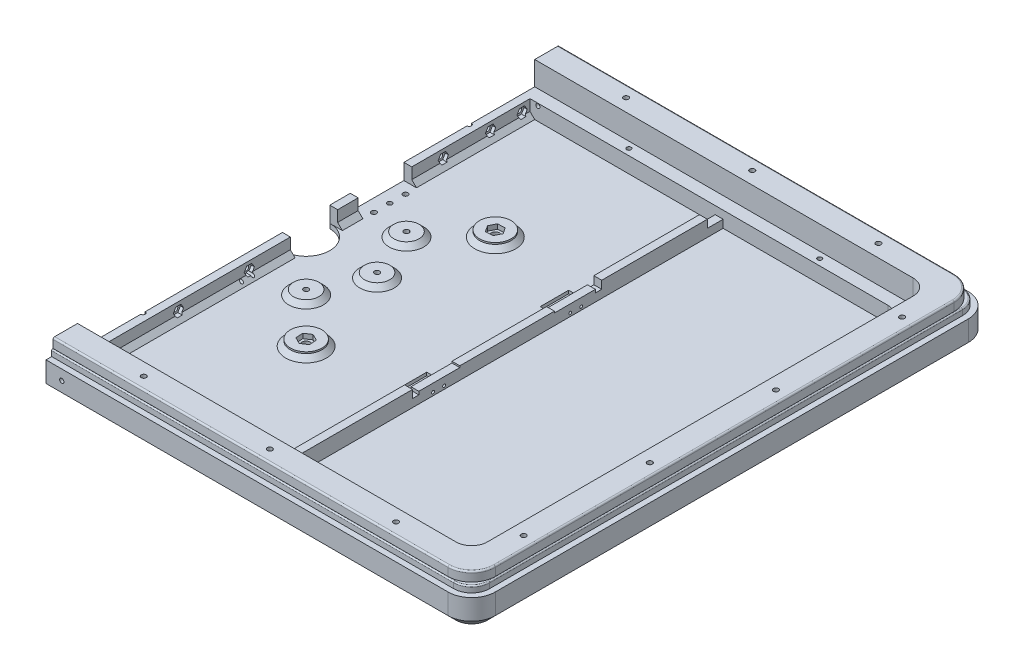
SolidWorks part; units mm, degrees
ref_plane "Front Plane" through (0, 0, 0) normal (0, 0, 1) x (1, 0, 0)
ref_plane "Top Plane" through (0, 0, 0) normal (0, 1, 0) x (1, 0, 0)
ref_plane "Right Plane" through (0, 0, 0) normal (1, 0, 0) x (0, 0, -1)
sketch "Sketch1" plane through (0, 0, 0) normal (0, 1, 0) x (1, 0, 0)
  line L1 (-270, -165) -> (270, -165)
  line L2 (-270, -165) -> (-270, 165)
  line L3 (-270, 165) -> (270, 165)
  line L4 (270, -165) -> (270, 165)
  line L5 (-270, -165) -> (270, 165) construction
  line L6 (-270, 165) -> (270, -165) construction
  point P0 (0, 0)
  dimension "D1" = 540
  dimension "D2" = 330
extrude "Boss-Extrude1" add sketch "Sketch1" along normal blind 3
sketch "Sketch2" plane through (0, 3, 0) normal (0, 1, 0) x (1, 0, 0)
  line L0 (250, 145) -> (-250, 145)
  line L1 (270, -165) -> (-270, -165)
  line L2 (270, -165) -> (270, 165)
  line L3 (270, 165) -> (-270, 165)
  line L4 (-270, -165) -> (-270, 165)
  line L5 (270, -165) -> (-270, 165) construction
  line L6 (270, 165) -> (-270, -165) construction
  line L7 (-250, -145) -> (-250, 145)
  line L8 (250, -145) -> (-250, -145)
  line L9 (250, -145) -> (250, 145)
  point P0 (0, 0)
  dimension "D1" = 20
  dimension "D2" = 540
extrude "Boss-Extrude2" add sketch "Sketch2" along normal blind 25 contours L0 L7 L8 L9 | L2 L1 L4 L3
fillet "Fillet1" radius 15 4 edges at (-270, 14, -165) (-270, 14, 165) (270, 14, 165) (270, 14, -165)
sketch "Sketch4" plane through (0, 28, 0) normal (0, 1, 0) x (1, 0, 0)
  line L0 (-270, 0) -> (-258, 0) construction
  line L1 (-270, -150) -> (-270, 150) construction
  line L2 (-258, 0) -> (-258, 40) construction
  line L3 (-258, 40) -> (-258, 120) construction
  line L4 (0, 0) -> (0, 145) construction
  line L5 (250, 145) -> (-250, 145) construction
  line L6 (0, 165) -> (0, 153) construction
  line L7 (255, 165) -> (-255, 165) construction
  line L8 (0, 153) -> (-50, 153) construction
  line L9 (-50, 153) -> (-130, 153) construction
  line L10 (-130, 153) -> (-210, 153) construction
  line L11 (130, 153) -> (210, 153) construction
  line L12 (50, 153) -> (130, 153) construction
  line L13 (258, 40) -> (258, 120) construction
  line L14 (0, 0) -> (78.1952, 0) construction
  line L15 (258, -40) -> (258, -120) construction
  line L16 (50, -153) -> (130, -153) construction
  line L17 (130, -153) -> (210, -153) construction
  line L18 (-130, -153) -> (-210, -153) construction
  line L19 (-50, -153) -> (-130, -153) construction
  line L20 (0, -153) -> (-50, -153) construction
  line L21 (0, -165) -> (0, -153) construction
  line L22 (-258, -40) -> (-258, -120) construction
  circle A0 centre (-258, 120) radius 1.6
  circle A1 centre (-258, 40) radius 1.6
  circle A2 centre (-210, 153) radius 1.6
  circle A3 centre (-130, 153) radius 1.6
  circle A4 centre (-50, 153) radius 1.6
  circle A5 centre (50, 153) radius 1.6
  circle A6 centre (130, 153) radius 1.6
  circle A7 centre (210, 153) radius 1.6
  circle A8 centre (258, 40) radius 1.6
  circle A9 centre (258, 120) radius 1.6
  circle A10 centre (258, -120) radius 1.6
  circle A11 centre (258, -40) radius 1.6
  circle A12 centre (210, -153) radius 1.6
  circle A13 centre (130, -153) radius 1.6
  circle A14 centre (50, -153) radius 1.6
  circle A15 centre (-50, -153) radius 1.6
  circle A16 centre (-130, -153) radius 1.6
  circle A17 centre (-210, -153) radius 1.6
  circle A18 centre (-258, -40) radius 1.6
  circle A19 centre (-258, -120) radius 1.6
  dimension "D1" = 50
  dimension "D2" = 80
  dimension "D3" = 80
  dimension "D4" = 12
  dimension "D5" = 12
  dimension "D6" = 40
  dimension "D7" = 80
extrude "Cut-Extrude1" cut sketch "Sketch4" against normal up to surface (28 mm away) up to face at (0, 0, 0)
sketch "Sketch5" plane through (0, 3, 0) normal (0, 1, 0) x (1, 0, 0)
  circle A0 centre (0, 0) radius 15
  dimension "D1" = 30
extrude "Cut-Extrude2" cut sketch "Sketch5" against normal up to surface (3 mm away) up to face at (-130, 0, 151.4)
chamfer "Chamfer1" distance 5 angle 45 8 edges at (270, 0, 0) (0, 0, -165) (0, 0, 165) (265.6066, 0, -160.6066) (265.6066, 0, 160.6066) (-265.6066, 0, -160.6066) (-265.6066, 0, 160.6066) (-270, 0, 0)
sketch "Sketch7" plane through (0, 0, 0) normal (0, -1, 0) x (1, 0, 0)
  line L1 (-60, -60) -> (60, -60) construction
  line L2 (-60, -60) -> (-60, 60) construction
  line L3 (-60, 60) -> (60, 60) construction
  line L4 (60, -60) -> (60, 60) construction
  line L5 (-60, -60) -> (60, 60) construction
  line L6 (-60, 60) -> (60, -60) construction
  circle A0 centre (-60, 60) radius 2.6
  circle A1 centre (60, 60) radius 2.6
  circle A2 centre (60, -60) radius 2.6
  circle A3 centre (-60, -60) radius 2.6
  point P0 (0, 0)
  dimension "D1" = 120
  dimension "D2" = 120
extrude "Cut-Extrude3" cut sketch "Sketch7" against normal up to surface (3 mm away) up to face at (0, 3, 15)
sketch "Sketch9" plane through (0, 0, 0) normal (0, -1, 0) x (1, 0, 0)
  line L0 (0, 0) -> (45, 0) construction
  line L1 (-31.8198, -31.8198) -> (31.8198, -31.8198) construction
  line L2 (-31.8198, -31.8198) -> (-31.8198, 31.8198) construction
  line L3 (-31.8198, 31.8198) -> (31.8198, 31.8198) construction
  line L4 (31.8198, -31.8198) -> (31.8198, 31.8198) construction
  line L5 (-31.8198, -31.8198) -> (31.8198, 31.8198) construction
  line L6 (-31.8198, 31.8198) -> (31.8198, -31.8198) construction
  line L7 (0, 0) -> (0, -31.8198) construction
  circle A0 centre (-31.8198, 31.8198) radius 1.6
  circle A1 centre (31.8198, 31.8198) radius 1.6
  circle A2 centre (31.8198, -31.8198) radius 1.6
  circle A3 centre (-31.8198, -31.8198) radius 1.6
  circle A4 centre (45, 0) radius 1.6
  circle A5 centre (-45, 0) radius 1.6
  point P0 (0, 0)
  dimension "D3" = 45
  dimension "D1" = 90
  dimension "D2" = 90
extrude "Cut-Extrude4" cut sketch "Sketch9" against normal blind 47
sketch "Sketch17" plane through (0, 28, 0) normal (0, 1, 0) x (1, 0, 0)
  line L0 (0, 0) -> (0, 165) construction
  line L1 (265, 165) -> (-265, 165) construction
sketch "Sketch18" plane through (0, 28, 0) normal (0, 1, 0) x (1, 0, 0)
  line L0 (0, 165) -> (0, -165) construction
  line L1 (265, 165) -> (-265, 165) construction
  line L2 (265, -165) -> (-265, -165) construction
sketch "Sketch19" plane through (0, 28, 0) normal (0, 1, 0) x (1, 0, 0)
  line L0 (250.5, 160.5) -> (-250.5, 160.5)
  line L1 (255, -165) -> (-255, -165)
  line L2 (270, -150) -> (270, 150)
  line L3 (255, 165) -> (-255, 165)
  line L4 (-270, -150) -> (-270, 150)
  line L5 (270, -165) -> (-270, 165) construction
  line L6 (270, 165) -> (-270, -165) construction
  line L7 (-265.5, -145.5) -> (-265.5, 145.5)
  line L8 (250.5, -160.5) -> (-250.5, -160.5)
  line L9 (265.5, -145.5) -> (265.5, 145.5)
  line L10 (255, 160.5) -> (-255, 160.5) construction
  line L11 (-265.5, -150) -> (-265.5, 150) construction
  line L12 (265.5, -150) -> (265.5, 150) construction
  line L13 (255, -160.5) -> (-255, -160.5) construction
  arc A0 (-270, -150) -> (-255, -165) centre (-255, -150) ccw
  arc A1 (255, -165) -> (270, -150) centre (255, -150) ccw
  arc A2 (270, 150) -> (255, 165) centre (255, 150) ccw
  arc A3 (-255, 165) -> (-270, 150) centre (-255, 150) ccw
  arc A4 (-255, 160.5) -> (-265.5, 150) centre (-255, 150) ccw construction
  arc A5 (-265.5, -150) -> (-255, -160.5) centre (-255, -150) ccw construction
  arc A6 (255, -160.5) -> (265.5, -150) centre (255, -150) ccw construction
  arc A7 (265.5, 150) -> (255, 160.5) centre (255, 150) ccw construction
  arc A8 (-250.5, 160.5) -> (-265.5, 145.5) centre (-250.5, 145.5) ccw
  arc A9 (265.5, 145.5) -> (250.5, 160.5) centre (250.5, 145.5) ccw
  arc A10 (265.5, -145.5) -> (250.5, -160.5) centre (250.5, -145.5) cw
  arc A11 (-250.5, -160.5) -> (-265.5, -145.5) centre (-250.5, -145.5) cw
  point P0 (0, 0)
  dimension "D3" = 15
  dimension "D5" = 15
  dimension "D6" = 15
  dimension "D7" = 15
  dimension "D8" = 15
  dimension "D1" = 330
  dimension "D2" = 540
  dimension "D4" = 4.5
extrude "Cut-Extrude5" cut sketch "Sketch19" against normal blind 10
fillet "Fillet2" radius 1 8 edges at (265.5, 28, 0) (0, 28, 160.5) (-265.5, 28, 0) (0, 28, -160.5) (261.1066, 28, -156.1066) (261.1066, 28, 156.1066) (-261.1066, 28, 156.1066) (-261.1066, 28, -156.1066)
sketch "Sketch20" plane through (0, 18, 0) normal (0, 1, 0) x (1, 0, 0)
  line L0 (0, 165) -> (0, -165) construction
  line L1 (-255, 165) -> (255, 165) construction
  line L2 (-270, 150) -> (-270, -150) construction
  line L3 (-255, -165) -> (255, -165) construction
  line L4 (270, 150) -> (270, -150) construction
  line L5 (-270, 165) -> (270, -165) construction
  line L6 (-270, -165) -> (270, 165) construction
  line L7 (-255, 161.4) -> (255, 161.4)
  line L8 (266.4, 150) -> (266.4, -150)
  line L9 (-255, -161.4) -> (255, -161.4)
  line L10 (-266.4, 150) -> (-266.4, -150)
  line L11 (-255, 157.9) -> (255, 157.9)
  line L12 (262.9, 150) -> (262.9, -150)
  line L13 (-255, -157.9) -> (255, -157.9)
  line L14 (-262.9, 150) -> (-262.9, -150)
  arc A0 (-270, -150) -> (-255, -165) centre (-255, -150) ccw construction
  arc A1 (270, -150) -> (255, -165) centre (255, -150) cw construction
  arc A2 (270, 150) -> (255, 165) centre (255, 150) ccw construction
  arc A3 (-255, 165) -> (-270, 150) centre (-255, 150) ccw construction
  arc A4 (266.4, 150) -> (255, 161.4) centre (255, 150) ccw
  arc A5 (266.4, -150) -> (255, -161.4) centre (255, -150) cw
  arc A6 (-266.4, -150) -> (-255, -161.4) centre (-255, -150) ccw
  arc A7 (-255, 161.4) -> (-266.4, 150) centre (-255, 150) ccw
  arc A8 (262.9, 150) -> (255, 157.9) centre (255, 150) ccw
  arc A9 (262.9, -150) -> (255, -157.9) centre (255, -150) cw
  arc A10 (-262.9, -150) -> (-255, -157.9) centre (-255, -150) ccw
  arc A11 (-255, 157.9) -> (-262.9, 150) centre (-255, 150) ccw
  point P0 (0, 0)
  dimension "D3" = 15
  dimension "D1" = 330
  dimension "D2" = 540
  dimension "D4" = 3.6
  dimension "D5" = 3.5
extrude "Boss-Extrude3" add sketch "Sketch20" along normal blind 4
fillet "Fillet4" radius 0.8 8 edges at (263.061, 22, -158.061) (266.4, 22, 0) (263.061, 22, 158.061) (0, 22, 161.4) (-263.061, 22, 158.061) (-266.4, 22, 0) (-263.061, 22, -158.061) (0, 22, -161.4)
sketch "Sketch23" plane through (0, 3, 0) normal (0, 1, 0) x (1, 0, 0)
  line L0 (250, 145) -> (-250, 145) construction
  line L1 (-5, -145) -> (5, -145)
  line L2 (-5, -145) -> (-5, 145)
  line L3 (-5, 145) -> (5, 145)
  line L4 (5, -145) -> (5, 145)
  line L5 (-5, -145) -> (5, 145) construction
  line L6 (-5, 145) -> (5, -145) construction
  line L7 (0, 0) -> (250, 0) construction
  line L8 (-5, -15) -> (5, -15)
  line L9 (-5, -15) -> (-5, 15)
  line L10 (-5, 15) -> (5, 15)
  line L11 (5, -15) -> (5, 15)
  line L12 (-5, -15) -> (5, 15) construction
  line L13 (-5, 15) -> (5, -15) construction
  line L14 (250, -145) -> (250, 145) construction
  line L15 (250, 145) -> (-250, 145) construction
  line L16 (122.5, -145) -> (127.5, -145)
  line L17 (122.5, -145) -> (122.5, 145)
  line L18 (122.5, 145) -> (127.5, 145)
  line L19 (127.5, -145) -> (127.5, 145)
  line L20 (122.5, -145) -> (127.5, 145) construction
  line L21 (122.5, 145) -> (127.5, -145) construction
  line L27 (0, 0) -> (0, 145) construction
  line L28 (-122.5, 145) -> (-127.5, 145)
  line L29 (-127.5, -145) -> (-127.5, 145)
  line L30 (-122.5, -145) -> (-127.5, -145)
  line L31 (-122.5, -145) -> (-122.5, 145)
  point P0 (0, 0)
  point P8 (0, 0)
  point P17 (125, 0)
  line M14 (-250, -145) -> (250, -145)
  line M16 (250, 145) -> (-250, 145)
  dimension "D1" = 30
  dimension "D2" = 10
  dimension "D3" = 5
extrude "Boss-Extrude4" add sketch "Sketch23" along normal blind 10 contours L2 L10 L4 M16 | L8 L2 L4 M14 | L17 L16 L19 L18 | L28 L29 L30 L31 region at (0, 3, 80) region at (0, 3, -80)
sketch "Sketch24" plane through (0, 3, 0) normal (0, 1, 0) x (1, 0, 0)
  line L0 (-242, 137) -> (242, 137)
  line L1 (-250, -145) -> (250, -145)
  line L2 (-250, -145) -> (-250, 145)
  line L3 (-250, 145) -> (250, 145)
  line L4 (250, -145) -> (250, 145)
  line L5 (-250, -145) -> (250, 145) construction
  line L6 (-250, 145) -> (250, -145) construction
  line L7 (242, -137) -> (242, 137)
  line L8 (-242, -137) -> (242, -137)
  line L9 (-242, -137) -> (-242, 137)
  point P0 (0, 0)
  dimension "D1" = 8
extrude "Boss-Extrude5" add sketch "Sketch24" along normal up to surface (10 mm away) up to face at (-125, 13, 0)
sketch "Sketch25" plane through (127.5, 0, 0) normal (1, 0, 0) x (0, 0, -1)
  line L0 (0, 5) -> (0, 13) construction
  line L1 (-150, 5) -> (150, 5) construction
  line L2 (-145, 13) -> (145, 13) construction
  line L3 (0, 13) -> (0, 5) construction
  line L4 (0, 5) -> (-40, 5) construction
  line L5 (-40, 5) -> (-47, 5) construction
  circle A0 centre (-47, 5) radius 0.9
  circle A1 centre (-40, 5) radius 0.9
  circle A2 centre (47, 5) radius 0.9
  circle A3 centre (40, 5) radius 0.9
  dimension "D1" = 8
  dimension "D2" = 40
  dimension "D3" = 7
extrude "Cut-Extrude6" cut sketch "Sketch25" against normal up to surface (255 mm away) up to face at (-127.5, 8, 0)
sketch "Sketch26" plane through (0, 3, 0) normal (0, 1, 0) x (1, 0, 0)
  line L0 (0, 0) -> (-122.5, 0) construction
  line L1 (-122.5, -137) -> (-122.5, 137) construction
  line L2 (-122.5, 0) -> (-122.5, 36) construction
  line L3 (-122.5, -137) -> (-122.5, 137) construction
  line L4 (-122.5, -54) -> (-112.5, -54)
  line L5 (-122.5, 36) -> (-112.5, 36)
  line L6 (-122.5, 36) -> (-122.5, 54)
  line L7 (-122.5, 54) -> (-112.5, 54)
  line L8 (-112.5, 36) -> (-112.5, 54)
  line L9 (-122.5, -36) -> (-112.5, -36)
  line L10 (-122.5, -36) -> (-122.5, -54)
  line L11 (-112.5, -36) -> (-112.5, -54)
  line L12 (0, 0) -> (0, 165) construction
  line L13 (122.5, -36) -> (122.5, -54)
  line L14 (122.5, -36) -> (112.5, -36)
  line L15 (112.5, -36) -> (112.5, -54)
  line L16 (122.5, -54) -> (112.5, -54)
  line L17 (122.5, 54) -> (112.5, 54)
  line L18 (112.5, 36) -> (112.5, 54)
  line L19 (122.5, 36) -> (112.5, 36)
  line L20 (122.5, 36) -> (122.5, 54)
  point P11 (-112.5, 45)
  dimension "D1" = 36
  dimension "D2" = 10
extrude "Cut-Extrude7" cut sketch "Sketch26" against normal blind 2
sketch "Sketch27" plane through (0, 13, 0) normal (0, 1, 0) x (1, 0, 0)
  line L0 (0, 0) -> (0, 165) construction
  line L1 (-122.5, 0) -> (-127.5, 0) construction
  line L2 (-122.5, -36) -> (-122.5, 36) construction
  line L3 (-127.5, -137) -> (-127.5, 137) construction
  line L4 (-127.5, -137) -> (-127.5, 137) construction
  line L5 (-122.5, -60) -> (-127.5, -60)
  line L6 (-122.5, -60) -> (-122.5, -30)
  line L7 (-122.5, 60) -> (-127.5, 60)
  line L8 (-127.5, -60) -> (-127.5, -30)
  line L9 (-122.5, -60) -> (-123.75, -30) construction
  line L10 (-122.5, 60) -> (-123.75, 30) construction
  line L11 (-127.5, 30) -> (-127.5, 60)
  line L12 (-127.5, -30) -> (-122.5, -30)
  line L14 (-127.5, 30) -> (-122.5, 30)
  line L16 (126.25, -30) -> (127.5, -60) construction
  line L17 (126.25, 30) -> (127.5, 60) construction
  line L18 (-126.25, 30) -> (-127.5, 60) construction
  line L19 (-126.25, -30) -> (-127.5, -60) construction
  line L20 (-122.5, 30) -> (-122.5, 60)
  line L21 (122.5, 60) -> (123.75, 30) construction
  line L22 (122.5, -60) -> (123.75, -30) construction
  line L23 (122.5, 0) -> (127.5, 0) construction
  line L24 (122.5, 30) -> (122.5, 60)
  line L25 (127.5, 30) -> (122.5, 30)
  line L26 (127.5, -30) -> (122.5, -30)
  line L27 (127.5, 30) -> (127.5, 60)
  line L28 (127.5, -60) -> (127.5, -30)
  line L29 (122.5, 60) -> (127.5, 60)
  line L30 (122.5, -60) -> (122.5, -30)
  line L31 (122.5, -60) -> (127.5, -60)
  point P10 (-125, 0)
  point P17 (-125, 0)
  point P40 (125, 0)
  dimension "D1" = 120
  dimension "D2" = 60
extrude "Cut-Extrude8" cut sketch "Sketch27" against normal blind 3
sketch "Sketch28" plane through (0, 13, 0) normal (0, 1, 0) x (1, 0, 0)
  line L1 (-127.5, 30) -> (-122.5, 30)
  line L2 (-127.5, 30) -> (-127.5, -30)
  line L3 (-127.5, -30) -> (-122.5, -30)
  line L4 (-122.5, 30) -> (-122.5, -30)
  line L5 (122.5, 30) -> (127.5, 30)
  line L6 (122.5, 30) -> (122.5, -30)
  line L7 (122.5, -30) -> (127.5, -30)
  line L8 (127.5, 30) -> (127.5, -30)
extrude "Cut-Extrude9" cut sketch "Sketch28" against normal blind 2
sketch "Sketch29" plane through (0, 10, 0) normal (0, 1, 0) x (1, 0, 0)
  line L0 (-122.5, 30) -> (-122.5, 60) construction
  line L1 (-127.5, 60) -> (-122.5, 60)
  line L2 (-127.5, 60) -> (-127.5, 56)
  line L3 (-127.5, 56) -> (-122.5, 56)
  line L4 (-122.5, 60) -> (-122.5, 56)
  line L5 (-122.5, -60) -> (-122.5, -30) construction
  line L6 (-127.5, -60) -> (-122.5, -60)
  line L7 (-127.5, -60) -> (-127.5, -56)
  line L8 (-127.5, -56) -> (-122.5, -56)
  line L9 (-122.5, -60) -> (-122.5, -56)
  line L10 (127.5, -60) -> (127.5, -30) construction
  line L11 (122.5, -60) -> (127.5, -60)
  line L12 (122.5, -60) -> (122.5, -56)
  line L13 (122.5, -56) -> (127.5, -56)
  line L14 (127.5, -60) -> (127.5, -56)
  line L15 (127.5, -137) -> (127.5, 137) construction
  line L16 (122.5, 60) -> (127.5, 60)
  line L17 (122.5, 60) -> (122.5, 56)
  line L18 (122.5, 56) -> (127.5, 56)
  line L19 (127.5, 60) -> (127.5, 56)
extrude "Cut-Extrude10" cut sketch "Sketch29" against normal blind 2
sketch "Sketch31" plane through (0, 13, 0) normal (0, 1, 0) x (1, 0, 0)
  line L0 (0, 165) -> (0, 45) construction
  line L1 (255, 165) -> (-255, 165) construction
  line L3 (-8, 62) -> (8, 62)
  line L4 (-8, 62) -> (-8, 28)
  line L5 (-8, 28) -> (8, 28)
  line L6 (8, 62) -> (8, 28)
  line L7 (-8, 62) -> (8, 28) construction
  line L8 (-8, 28) -> (8, 62) construction
  point P11 (0, 0)
  point P12 (0, 0)
  dimension "D1" = 120
  dimension "D2" = 34
  dimension "D3" = 16
  dimension "D4" = 16
sketch "Sketch32" plane through (-270, 0, 0) normal (-1, 0, 0) x (0, 0, 1)
  line L0 (-30, 13) -> (-30, 18) construction
  line L1 (-62, 13) -> (-28, 13) construction
  line L2 (-150, 18) -> (150, 18) construction
  line L3 (-30, 18) -> (-30, 51) construction
extrude "Boss-Extrude6" add sketch "Sketch31" along normal blind 53 and the other way up to surface (10 mm away) other way up to face at (-60, 3, 57.4)
fillet "Fillet5" radius 15 2 edges at (0, 66, -28) (0, 66, -62)
sketch "Sketch34" plane through (-8, 0, 0) normal (-1, 0, 0) x (0, 0, 1)
  line L0 (-165, 18) -> (-45, 18) construction
  line L1 (-150, 18) -> (150, 18) construction
  line L2 (-45, 18) -> (-45, 53) construction
  circle A0 centre (-45, 53) radius 3
  dimension "D3" = 6
  dimension "D1" = 120
  dimension "D2" = 35
extrude "Cut-Extrude11" cut sketch "Sketch34" against normal blind 53
sketch "Sketch35" plane through (0, 3, 0) normal (0, 1, 0) x (1, 0, 0)
  circle A0 centre (-31.8198, 31.8198) radius 1.6
  circle A1 centre (-31.8198, 31.8198) radius 8
  circle A2 centre (31.8198, 31.8198) radius 1.6
  circle A3 centre (31.8198, 31.8198) radius 8
  circle A4 centre (31.8198, -31.8198) radius 1.6
  circle A5 centre (31.8198, -31.8198) radius 8
  circle A6 centre (-31.8198, -31.8198) radius 1.6
  circle A7 centre (-31.8198, -31.8198) radius 8
  circle A8 centre (-45, 0) radius 8
  circle A9 centre (45, 0) radius 8
  circle A10 centre (45, 0) radius 1.6
  circle A11 centre (-45, 0) radius 1.6
  point P16 (0, 0)
  dimension "D1" = 16
  dimension "D2" = 3.2
  dimension "D3" = 4
extrude "Boss-Extrude7" add sketch "Sketch35" along normal blind 3
chamfer "Chamfer2" distance 3 angle 45 6 edges at (31.8198, 3, 23.8198) (-31.8198, 3, 23.8198) (-31.8198, 3, -39.8198) (31.8198, 3, -39.8198) (45, 3, -8) (-45, 3, -8)
sketch "Sketch37" plane through (0, 66, 0) normal (0, 1, 0) x (1, 0, 0)
  line L0 (0, 47) -> (0, 43) construction
  line L1 (8, 47) -> (-8, 47) construction
  line L2 (-8, 43) -> (8, 43) construction
  line L4 (-8, 28) -> (8, 28)
  line L5 (-8, 28) -> (-8, 62)
  line L6 (-8, 62) -> (8, 62)
  line L7 (8, 28) -> (8, 62)
  line L8 (-8, 28) -> (8, 62) construction
  line L9 (-8, 62) -> (8, 28) construction
  point P6 (0, 45)
extrude "Cut-Extrude12" cut sketch "Sketch37" against normal up to surface (63 mm away) up to face at (-45, 3, -11)
sketch "Sketch38" plane through (0, 3, 0) normal (0, 1, 0) x (1, 0, 0)
  line L0 (0, 62) -> (0, 28) construction
  line L1 (5, 62) -> (-5, 62) construction
  line L2 (-5, 28) -> (5, 28) construction
  line L3 (0, 28) -> (0, 45) construction
  line L4 (0, 45) -> (8, 45) construction
  line L5 (8, 45) -> (8, 55) construction
  circle A0 centre (8, 55) radius 1.6
  circle A1 centre (8, 35) radius 1.6
  circle A2 centre (-8, 35) radius 1.6
  circle A3 centre (-8, 55) radius 1.6
  circle A4 centre (8, 45) radius 1.5
  circle A5 centre (-8, 45) radius 1.5
  dimension "D2" = 10
  dimension "D1" = 8
extrude "Cut-Extrude13" cut sketch "Sketch38" against normal blind 90
chamfer "Chamfer3" distance 3 angle 45 6 edges at (-5, 3, 76) (-5, 3, -21.5) (5, 3, -21.5) (5, 3, 76) (5, 3, -99.5) (-5, 3, -99.5)
sketch "Sketch39" plane through (0, 13, 0) normal (0, 1, 0) x (1, 0, 0)
  line L0 (-242, 0) -> (-242, 137) construction
  line L1 (-242, 137) -> (-242, -137) construction
  line L2 (-242, 137) -> (-242, 68.5) construction
  line L3 (-242, 68.5) -> (-250, 68.5) construction
  line L4 (-250, -145) -> (-250, 145) construction
  line L5 (-184.75, 137) -> (-184.75, 145) construction
  line L6 (-127.5, 137) -> (-242, 137) construction
  line L7 (250, 145) -> (-250, 145) construction
  line L8 (-63.75, 137) -> (-63.75, 145) construction
  line L10 (-5, 137) -> (-122.5, 137) construction
  line L11 (250, 145) -> (-250, 145) construction
  line L12 (0, 0) -> (0, 145) construction
  line L13 (63.75, 137) -> (63.75, 145) construction
  line L14 (184.75, 137) -> (184.75, 145) construction
  line L15 (242, 68.5) -> (250, 68.5) construction
  line L16 (242, 137) -> (242, 68.5) construction
  line L17 (0, 62) -> (0, 145) construction
  line L18 (5, 62) -> (-5, 62) construction
  line L19 (0, 0) -> (250, 0) construction
  line L20 (250, -145) -> (250, 145) construction
  line L21 (0, -62) -> (0, -145) construction
  line L22 (242, -137) -> (242, -68.5) construction
  line L23 (242, -68.5) -> (250, -68.5) construction
  line L24 (184.75, -137) -> (184.75, -145) construction
  line L25 (63.75, -137) -> (63.75, -145) construction
  line L26 (-63.75, -137) -> (-63.75, -145) construction
  line L27 (-184.75, -137) -> (-184.75, -145) construction
  line L28 (-242, -68.5) -> (-250, -68.5) construction
  line L29 (-242, -137) -> (-242, -68.5) construction
  circle A0 centre (-246, 68.5) radius 1.4
  circle A1 centre (-184.75, 141) radius 1.4
  circle A2 centre (-63.75, 141) radius 1.4
  circle A3 centre (63.75, 141) radius 1.4
  circle A4 centre (184.75, 141) radius 1.4
  circle A5 centre (246, 68.5) radius 1.4
  circle A6 centre (0, 103.5) radius 1.4
  circle A7 centre (0, -103.5) radius 1.4
  circle A8 centre (246, -68.5) radius 1.4
  circle A9 centre (184.75, -141) radius 1.4
  circle A10 centre (63.75, -141) radius 1.4
  circle A11 centre (-63.75, -141) radius 1.4
  circle A12 centre (-184.75, -141) radius 1.4
  circle A13 centre (-246, -68.5) radius 1.4
extrude "Cut-Extrude14" cut sketch "Sketch39" against normal blind 8
fillet "Fillet6" radius 10 4 edges at (-242, 8, -137) (-242, 8, 137) (242, 8, 137) (242, 8, -137)
fillet "Fillet7" radius 10 4 edges at (250, 20.5, 145) (250, 20.5, -145) (-250, 20.5, 145) (-250, 20.5, -145)
sketch "Sketch41" plane through (0, 0, 0) normal (1, 0, 0) x (0, 0, -1)
  line L0 (165, 11.5) -> (153, 11.5) construction
  line L1 (165, 18) -> (165, 5) construction
  line L2 (0, 0) -> (0, 98.4706) construction
  circle A0 centre (153, 11.5) radius 5
  circle A1 centre (-153, 11.5) radius 5
  dimension "D1" = 12
extrude "Cut-Extrude15" cut sketch "Sketch41" against normal blind 30 and the other way blind 30
sketch "Sketch42" plane through (5, 0, 0) normal (1, 0, 0) x (0, 0, -1)
  line L0 (-132, 3) -> (-132, 13) construction
  line L1 (-127, 3) -> (-137, 3) construction
  line L2 (-135, 13) -> (135, 13) construction
  line L3 (-102.1, 13) -> (-69.9, 13) construction
  line L4 (-69.9, 13) -> (-86, 13) construction
  line L5 (-86, 13) -> (-86, 3) construction
  line L6 (-127, 3) -> (127, 3) construction
  line L7 (-67.1, 13) -> (-15, 13) construction
  line L8 (-15, 13) -> (-41.05, 13) construction
  line L9 (-41.05, 13) -> (-41.05, 3) construction
  line L10 (145, 13) -> (145, 3) construction
  line L11 (145, 3) -> (145, 8) construction
  line L12 (145, 8) -> (132, 8) construction
  line L13 (132, 8) -> (112, 8) construction
  line L14 (112, 8) -> (82, 8) construction
  circle A0 centre (112, 8) radius 1.6
  circle A1 centre (132, 8) radius 1.6
  circle A2 centre (82, 8) radius 1.6
  circle A3 centre (-86, 8) radius 1.6
  circle A4 centre (-132, 8) radius 1.6
  circle A5 centre (-41.05, 8) radius 1.6
  dimension "D1" = 30
  dimension "D2" = 20
  dimension "D3" = 13
extrude "Cut-Extrude16" cut sketch "Sketch42" against normal blind 30 and the other way blind 10
sketch "Sketch43" plane through (5, 0, 0) normal (1, 0, 0) x (0, 0, -1)
  line L0 (-87.6166, 10.8) -> (-89.2332, 8)
  line L1 (-128.7668, 8) -> (-130.3834, 10.8)
  line L2 (-130.3834, 10.8) -> (-133.6166, 10.8)
  line L3 (-133.6166, 10.8) -> (-135.2332, 8)
  line L4 (-135.2332, 8) -> (-133.6166, 5.2)
  line L5 (-133.6166, 5.2) -> (-130.3834, 5.2)
  line L6 (-130.3834, 5.2) -> (-128.7668, 8)
  line L7 (-89.2332, 8) -> (-87.6166, 5.2)
  line L8 (-87.6166, 5.2) -> (-84.3834, 5.2)
  line L9 (-82.7668, 8) -> (-84.3834, 10.8)
  line L10 (-84.3834, 10.8) -> (-87.6166, 10.8)
  line L11 (-84.3834, 5.2) -> (-82.7668, 8)
  line L12 (-37.8168, 8) -> (-39.4334, 10.8)
  line L13 (-39.4334, 5.2) -> (-37.8168, 8)
  line L14 (-42.6666, 10.8) -> (-44.2832, 8)
  line L15 (-39.4334, 10.8) -> (-42.6666, 10.8)
  line L16 (-42.6666, 5.2) -> (-39.4334, 5.2)
  line L17 (-44.2832, 8) -> (-42.6666, 5.2)
  line L18 (85.2332, 8) -> (83.6166, 10.8)
  line L19 (83.6166, 5.2) -> (85.2332, 8)
  line L20 (80.3834, 10.8) -> (78.7668, 8)
  line L21 (83.6166, 10.8) -> (80.3834, 10.8)
  line L22 (80.3834, 5.2) -> (83.6166, 5.2)
  line L23 (78.7668, 8) -> (80.3834, 5.2)
  line L24 (115.2332, 8) -> (113.6166, 10.8)
  line L25 (113.6166, 5.2) -> (115.2332, 8)
  line L26 (110.3834, 10.8) -> (108.7668, 8)
  line L27 (113.6166, 10.8) -> (110.3834, 10.8)
  line L28 (110.3834, 5.2) -> (113.6166, 5.2)
  line L29 (108.7668, 8) -> (110.3834, 5.2)
  line L30 (82, 8) -> (112, 8) construction
  line L31 (112, 8) -> (132, 8) construction
  line L32 (130.3834, 10.8) -> (128.7668, 8)
  line L33 (130.3834, 5.2) -> (133.6166, 5.2)
  line L34 (135.2332, 8) -> (133.6166, 10.8)
  line L35 (133.6166, 10.8) -> (130.3834, 10.8)
  line L36 (128.7668, 8) -> (130.3834, 5.2)
  line L37 (133.6166, 5.2) -> (135.2332, 8)
  circle A0 centre (-132, 8) radius 2.8 construction
  circle A1 centre (-86, 8) radius 2.8 construction
  circle A2 centre (-41.05, 8) radius 2.8 construction
  circle A3 centre (82, 8) radius 2.8 construction
  circle A4 centre (112, 8) radius 2.8 construction
  circle A5 centre (132, 8) radius 2.8 construction
  dimension "D1" = 5.6
extrude "Cut-Extrude17" cut sketch "Sketch43" against normal blind 2 and the other way blind 17
sketch "Sketch45" plane through (0, 3, 0) normal (0, 1, 0) x (1, 0, 0)
  circle A0 centre (-60, 60) radius 10
  circle A1 centre (-60, 60) radius 2.6
  circle A2 centre (60, 60) radius 10
  circle A3 centre (60, 60) radius 2.6
  circle A4 centre (60, -60) radius 10
  circle A5 centre (60, -60) radius 2.6
  circle A6 centre (-60, -60) radius 10
  circle A7 centre (-60, -60) radius 2.6
  point P16 (0, 0)
  dimension "D1" = 20
  dimension "D2" = 4
extrude "Boss-Extrude8" add sketch "Sketch45" along normal blind 4
chamfer "Chamfer4" distance 3 angle 45 4 edges at (-60, 3, -70) (60, 3, -70) (-60, 3, 50) (60, 3, 50)
sketch "Sketch48" plane through (0, 7, 0) normal (0, 1, 0) x (1, 0, 0)
  line L0 (62.567, 56.091) -> (64.6688, 60.2686)
  line L1 (-56.091, 62.567) -> (-60.2686, 64.6688)
  line L2 (-60.2686, 64.6688) -> (-64.1776, 62.1018)
  line L3 (-64.1776, 62.1018) -> (-63.909, 57.433)
  line L4 (-63.909, 57.433) -> (-59.7314, 55.3312)
  line L5 (-59.7314, 55.3312) -> (-55.8224, 57.8982)
  line L6 (-55.8224, 57.8982) -> (-56.091, 62.567)
  line L7 (64.6688, 60.2686) -> (62.1018, 64.1776)
  line L8 (62.1018, 64.1776) -> (57.433, 63.909)
  line L9 (57.433, 63.909) -> (55.3312, 59.7314)
  line L10 (55.3312, 59.7314) -> (57.8982, 55.8224)
  line L11 (57.8982, 55.8224) -> (62.567, 56.091)
  line L12 (56.091, -62.567) -> (60.2686, -64.6688)
  line L13 (60.2686, -64.6688) -> (64.1776, -62.1018)
  line L14 (64.1776, -62.1018) -> (63.909, -57.433)
  line L15 (63.909, -57.433) -> (59.7314, -55.3312)
  line L16 (59.7314, -55.3312) -> (55.8224, -57.8982)
  line L17 (55.8224, -57.8982) -> (56.091, -62.567)
  line L18 (-62.567, -56.091) -> (-64.6688, -60.2686)
  line L19 (-64.6688, -60.2686) -> (-62.1018, -64.1776)
  line L20 (-62.1018, -64.1776) -> (-57.433, -63.909)
  line L21 (-57.433, -63.909) -> (-55.3312, -59.7314)
  line L22 (-55.3312, -59.7314) -> (-57.8982, -55.8224)
  line L23 (-57.8982, -55.8224) -> (-62.567, -56.091)
  circle A0 centre (-60, 60) radius 4.05 construction
  circle A1 centre (60, 60) radius 4.05 construction
  circle A2 centre (60, -60) radius 4.05 construction
  circle A3 centre (-60, -60) radius 4.05 construction
  point P36 (0, 0)
  dimension "D1" = 8.1
  dimension "D2" = 4
extrude "Cut-Extrude18" cut sketch "Sketch48" against normal blind 3
sketch "Sketch49" plane through (0, 0, 0) normal (0, -1, 0) x (1, 0, 0)
  circle A0 centre (0, 0) radius 60
sketch "Sketch50" plane through (0, 0, 0) normal (0, -1, 0) x (1, 0, 0)
  line L1 (-60, 60) -> (60, 60) construction
sketch "Sketch52" plane through (0, 0, 165) normal (0, 0, 1) x (1, 0, 0)
  line L0 (0, 5) -> (0, 18) construction
  line L1 (-255, 5) -> (255, 5) construction
  line L2 (-255, 18) -> (255, 18) construction
  line L3 (0, 18) -> (0, 11.5) construction
  line L4 (0, 11.5) -> (-10, 11.5) construction
  circle A0 centre (-10, 11.5) radius 1.35
  circle A1 centre (10, 11.5) radius 1.35
  dimension "D2" = 2.7
  dimension "D1" = 10
extrude "Cut-Extrude20" cut sketch "Sketch52" against normal up to surface (330 mm away) contours A0 | A1 region at (-10, 11.5, 165) up to face at (0, 11.5, -165)
sketch "Sketch51" plane through (0, 28, 0) normal (0, 1, 0) x (1, 0, 0)
  line L0 (0, 0) -> (0, 165) construction
  line L1 (255, 165) -> (-255, 165) construction
  line L3 (0, 165) -> (-382.0393, 165)
  line L4 (0, 165) -> (0, -215.5506)
  line L5 (0, -215.5506) -> (-382.0393, -215.5506)
  line L6 (-382.0393, 165) -> (-382.0393, -215.5506)
  point P8 (-382.0393, -215.5506)
extrude "Cut-Extrude21" cut sketch "Sketch51" against normal up to surface (28 mm away) up to face at (8, 0, -36.6)
sketch "Sketch53" plane through (0, 13, 0) normal (0, 1, 0) x (1, 0, 0)
  line L0 (127.5, 60) -> (127.5, 137) construction
  line L1 (122.5, 137) -> (127.5, 137)
  line L2 (122.5, 137) -> (122.5, 127)
  line L3 (122.5, 127) -> (127.5, 127)
  line L4 (127.5, 137) -> (127.5, 127)
extrude "Cut-Extrude22" cut sketch "Sketch53" against normal blind 5
